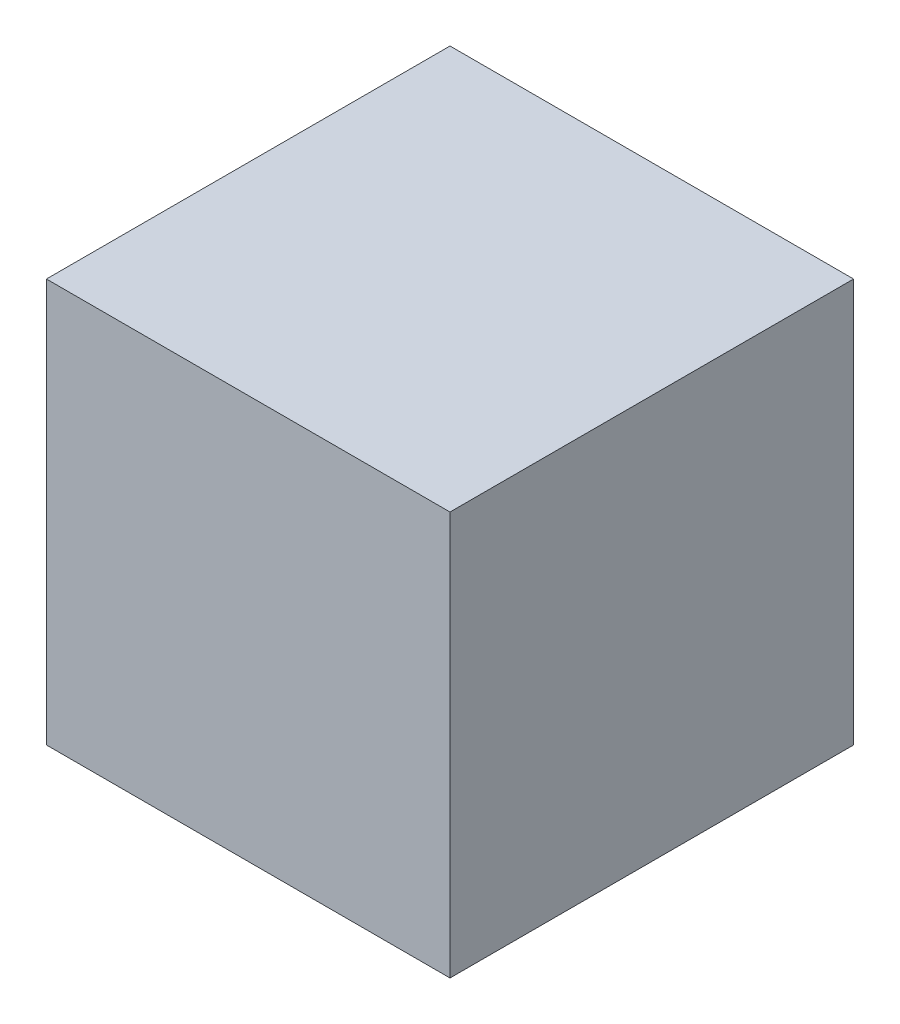
SolidWorks part; units mm, degrees
ref_plane "Plano frontal" through (0, 0, 0) normal (0, 0, 1) x (1, 0, 0)
ref_plane "Plano superior" through (0, 0, 0) normal (0, 1, 0) x (1, 0, 0)
ref_plane "Plano direito" through (0, 0, 0) normal (1, 0, 0) x (0, 0, -1)
sketch "Esboço1" plane through (0, 0, 0) normal (0, 0, 1) x (1, 0, 0)
  line L1 (0, 0) -> (100, 0)
  line L2 (0, 0) -> (0, 100)
  line L3 (0, 100) -> (100, 100)
  line L4 (100, 0) -> (100, 100)
extrude "Ressalto-extrusão1" add sketch "Esboço1" along normal blind 100
